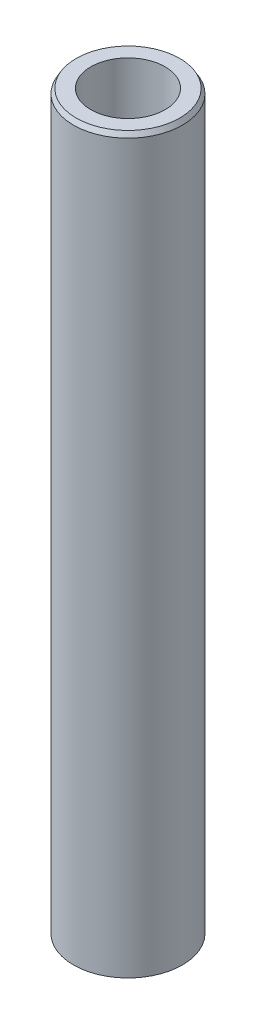
SolidWorks part; units mm, degrees
ref_plane "Front Plane" through (0, 0, 0) normal (0, 0, 1) x (1, 0, 0)
ref_plane "Top Plane" through (0, 0, 0) normal (0, 1, 0) x (1, 0, 0)
ref_plane "Right Plane" through (0, 0, 0) normal (1, 0, 0) x (0, 0, -1)
sketch "Sketch1" plane through (0, 0, 0) normal (0, 1, 0) x (1, 0, 0)
  circle A0 centre (0, 0) radius 20
  dimension "SHAFT_OD" = 40
extrude "Boss-Extrude1" add sketch "Sketch1" along normal blind 269.7873
sketch "Sketch2" plane through (0, 0, 0) normal (0, 1, 0) x (1, 0, 0)
  circle A0 centre (0, 0) radius 13.6537
  dimension "BORE_D" = 27.3073
extrude "Cut-Extrude1" cut sketch "Sketch2" along normal through all
chamfer "Chamfer1" distance 1.7433 angle 30 2 edges at (0, 269.7873, 20) (0, 0, 20) first distance on face at (0, 269.7873, 20) first distance on face at (0, 0, 13.6537)
